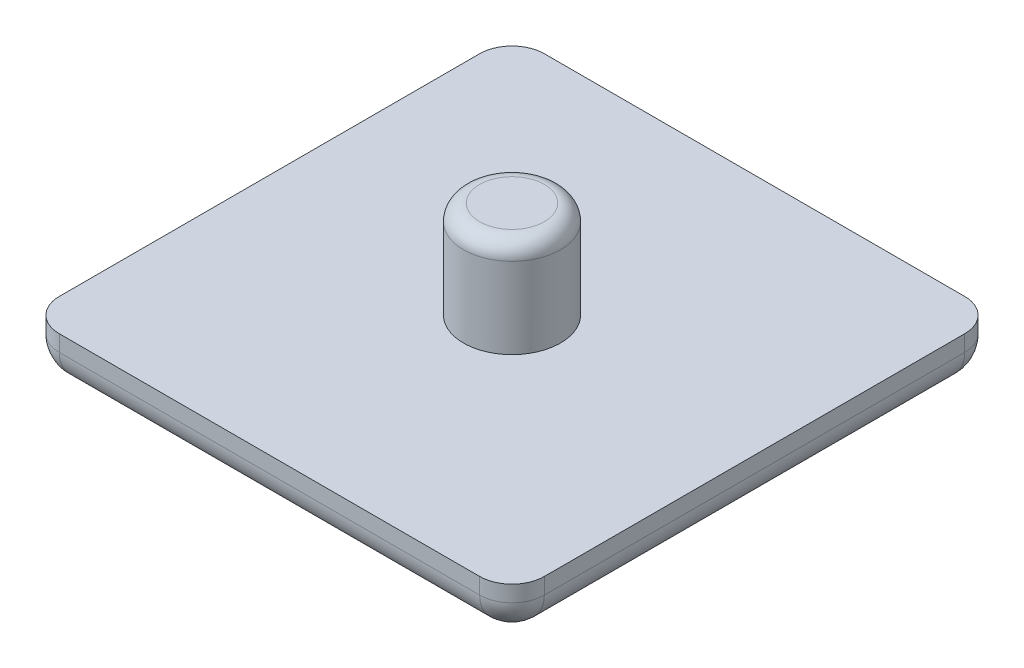
SolidWorks part; units mm, degrees
ref_plane "Front Plane" through (0, 0, 0) normal (0, 0, 1) x (1, 0, 0)
ref_plane "Top Plane" through (0, 0, 0) normal (0, 1, 0) x (1, 0, 0)
ref_plane "Right Plane" through (0, 0, 0) normal (1, 0, 0) x (0, 0, -1)
sketch "Sketch1" plane through (0, 0, 0) normal (0, 1, 0) x (1, 0, 0)
  line L1 (0, 0) -> (30, 0)
  line L2 (0, 0) -> (0, 30)
  line L3 (0, 30) -> (30, 30)
  line L4 (30, 0) -> (30, 30)
  dimension "D1" = 30
  dimension "D2" = 30
extrude "Boss-Extrude1" add sketch "Sketch1" along normal blind 3
sketch "Sketch3" plane through (0, 3, 0) normal (0, 1, 0) x (1, 0, 0)
  circle A0 centre (15, 15) radius 3
  dimension "D1" = 6
extrude "Boss-Extrude2" add sketch "Sketch3" along normal blind 6
fillet "Fillet2" radius 1 1 edges at (15, 9, -12) type face fillet first side face at (15, 9, -12) second side face at (15, 9, -12)
fillet "Fillet3" radius 2 2 edges at (0, 0, -15) (15, 0, 0) type face fillet first side face at (0, 1.5, -15) first side face at (15, 1.5, 0) second side face at (15, 0, -15)
fillet "Fillet4" radius 2 2 edges at (30, 0, -16) (16, 0, -30) type face fillet first side face at (12.3172, 1.5172, -30) first side face at (30, 1.5172, -12.3172) second side face at (16, 0, -16)
fillet "Fillet5" radius 2 1 edges at (0.5858, 0.5858, -0.5858) type face fillet first side face at (0.7929, 0.7929, -14.3964) second side face at (14.3964, 0.7929, -0.7929)
fillet "Fillet6" radius 2 1 edges at (29.4142, 0.5858, -29.4142) type face fillet first side face at (29.2071, 0.7929, -15.6036) second side face at (15.6036, 0.7929, -29.2071)
